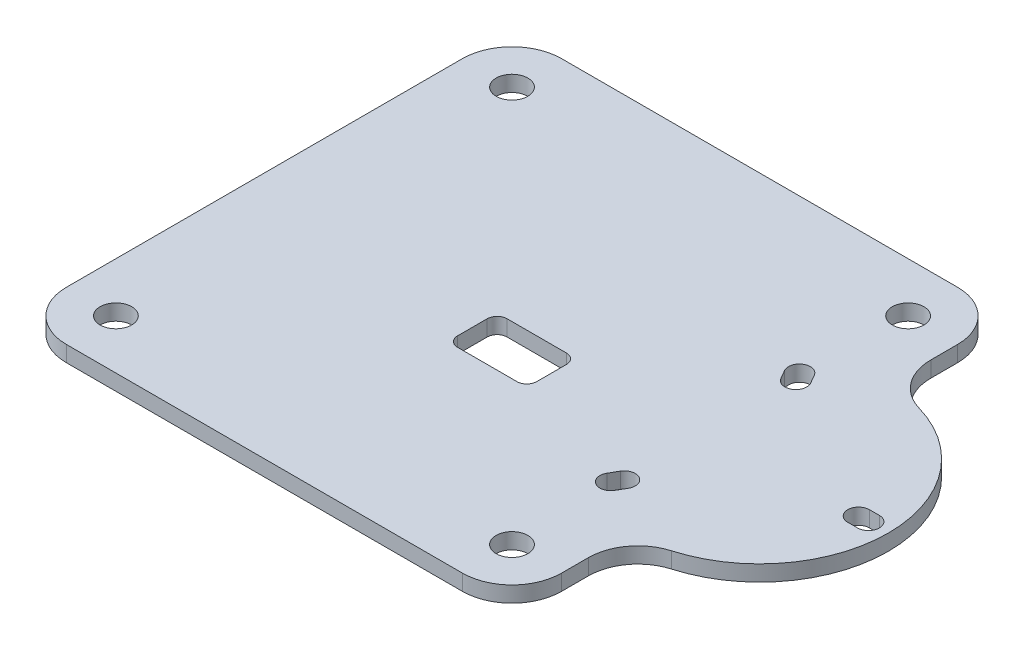
SolidWorks part; units mm, degrees
ref_plane "Front Plane" through (0, 0, 0) normal (0, 0, 1) x (1, 0, 0)
ref_plane "Top Plane" through (0, 0, 0) normal (0, 1, 0) x (1, 0, 0)
ref_plane "Right Plane" through (0, 0, 0) normal (1, 0, 0) x (0, 0, -1)
sketch "Sketch1" plane through (0, 0, 0) normal (0, 1, 0) x (1, 0, 0)
  line L1 (-50, 25) -> (-50, -25)
  line L3 (-50, 0) -> (0, 0) construction
  line L4 (0, 13) -> (0, 25)
  line L5 (0, 25) -> (-50, 25)
  line L6 (0, -13) -> (0, -25)
  line L7 (0, -25) -> (-50, -25)
  arc A0 (0, -13) -> (0, 13) centre (0, 0) ccw
  dimension "D2" = 26
  dimension "D1" = 50
  dimension "D3" = 50
extrude "Boss-Extrude1" add sketch "Sketch1" along normal blind 1.6
ref_axis "Axis1" through (0, -0.2678, 0) along (0, 1, 0)
fillet "Fillet1" radius 5 4 edges at (-50, 0.8, 25) (-50, 0.8, -25) (0, 0.8, -25) (0, 0.8, 25)
sketch "Sketch2" plane through (0, 0, 0) normal (0, 1, 0) x (1, 0, 0)
  line L0 (10.5, 0) -> (0, 0) construction
  line L1 (0, 0) -> (-5.25, 9.0933) construction
  line L2 (0, 0) -> (-5.25, -9.0933) construction
  line L3 (-5.5, -9.5263) -> (-5, -8.6603) construction
  line L4 (-6.4526, -8.9763) -> (-5.9526, -8.1103)
  line L5 (-4.5474, -10.0763) -> (-4.0474, -9.2103)
  line L6 (10, 0) -> (11, 0) construction
  line L7 (10, 1.1) -> (11, 1.1)
  line L8 (10, -1.1) -> (11, -1.1)
  line L9 (-5, 8.6603) -> (-5.5, 9.5263) construction
  line L10 (-5.9526, 8.1103) -> (-6.4526, 8.9763)
  line L11 (-4.0474, 9.2103) -> (-4.5474, 10.0763)
  circle A3 centre (0, 0) radius 10.5 construction
  arc A4 (-6.4526, -8.9763) -> (-4.5474, -10.0763) centre (-5.5, -9.5263) ccw
  arc A5 (-4.0474, -9.2103) -> (-5.9526, -8.1103) centre (-5, -8.6603) ccw
  arc A6 (10, 1.1) -> (10, -1.1) centre (10, 0) ccw
  arc A7 (11, -1.1) -> (11, 1.1) centre (11, 0) ccw
  arc A8 (-5.9526, 8.1103) -> (-4.0474, 9.2103) centre (-5, 8.6603) ccw
  arc A9 (-4.5474, 10.0763) -> (-6.4526, 8.9763) centre (-5.5, 9.5263) ccw
  point P11 (-5.25, -9.0933)
  point P16 (10.5, 0)
  point P22 (-5.25, 9.0933)
  dimension "D3" = 1
  dimension "D4" = 21
  dimension "D6" = 1
  dimension "D1" = 120
  dimension "D2" = 120
  dimension "D5" = 2.2
  dimension "D7" = 2.2
  dimension "D8" = 2.2
  dimension "D9" = 1
extrude "Cut-Extrude1" cut sketch "Sketch2" along normal through all
sketch "Sketch3" plane through (0, 0, 0) normal (0, 1, 0) x (1, 0, 0)
  line L0 (-5, 0) -> (0, 0) construction
  line L1 (-45, 20) -> (-5, 20) construction
  line L2 (-45, 20) -> (-45, -20) construction
  line L3 (-45, -20) -> (-5, -20) construction
  line L4 (-5, 20) -> (-5, -20) construction
  line L6 (-50, 25) -> (-50, -25) construction
  line L7 (0, 25) -> (-50, 25) construction
  line L8 (0, 13) -> (0, 25) construction
  circle A0 centre (-45, 20) radius 1.6
  circle A1 centre (-5, 20) radius 1.6
  circle A2 centre (-5, -20) radius 1.6
  circle A3 centre (-45, -20) radius 1.6
  dimension "D4" = 3.2
  dimension "D1" = 5
  dimension "D2" = 5
  dimension "D3" = 5
extrude "Cut-Extrude2" cut sketch "Sketch3" along normal through all
fillet "Fillet2" radius 5 2 edges at (0, 0.8, -13) (0, 0.8, 13)
sketch "Sketch4" plane through (0, 0, 0) normal (0, -1, 0) x (1, 0, 0)
  line L1 (-26, 5.5) -> (-18, 5.5)
  line L2 (-26, 5.5) -> (-26, 0.5)
  line L3 (-26, 0.5) -> (-18, 0.5)
  line L4 (-18, 5.5) -> (-18, 0.5)
  dimension "D1" = 8
  dimension "D2" = 5
  dimension "D3" = 18
  dimension "D4" = 0.5
extrude "Cut-Extrude3" cut sketch "Sketch4" against normal through all
fillet "Fillet3" radius 1 4 edges at (-18, 0.8, 5.5) (-18, 0.8, 0.5) (-26, 0.8, 0.5) (-26, 0.8, 5.5)
